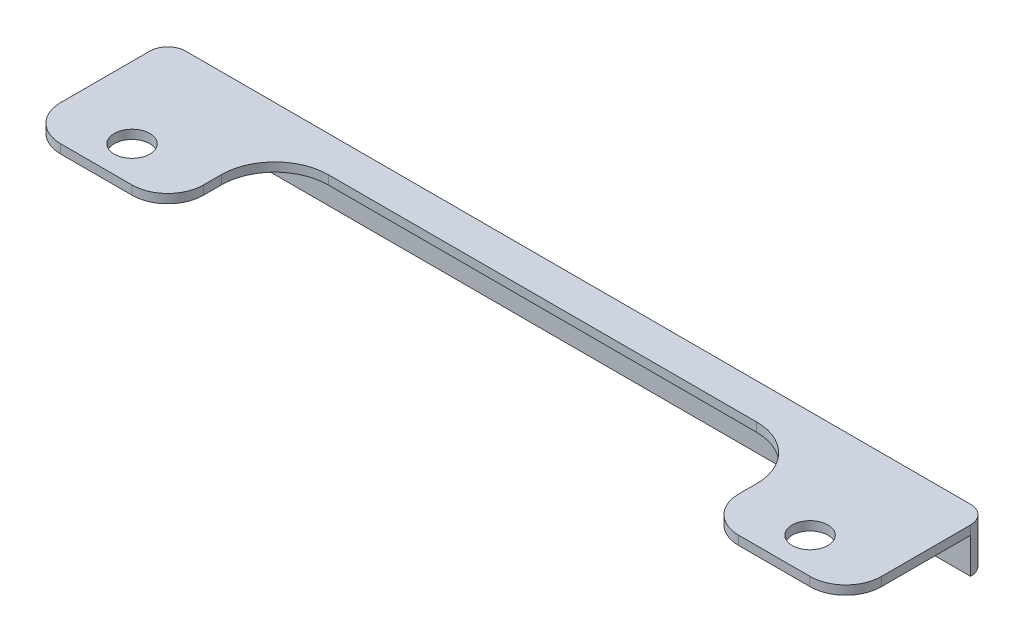
SolidWorks part; units mm, degrees
other "Markup1"
sketch "Sketch13" plane through (162.5103, 0, -104.1871) normal (0.0469, 0.9988, -0.0111) x (0.9947, -0.0457, 0.0919)
ref_plane "Front Plane" through (0, 0, 0) normal (0, 0, 1) x (1, 0, 0)
ref_plane "Top Plane" through (0, 0, 0) normal (0, 1, 0) x (1, 0, 0)
ref_plane "Right Plane" through (0, 0, 0) normal (1, 0, 0) x (0, 0, -1)
sketch "Sketch1" plane through (0, 0, 0) normal (0, 1, 0) x (1, 0, 0)
  line L0 (-88.0488, 103.273) -> (161.9512, 103.273)
  line L1 (-88.0488, 103.273) -> (-88.0488, 53.273)
  line L2 (161.9512, 103.273) -> (161.9512, 53.273)
  line L3 (-88.0488, 53.273) -> (-38.0488, 53.273)
  line L4 (-38.0488, 53.273) -> (-38.0488, 93.273)
  line L5 (36.9512, 136.3536) -> (36.9512, 9.8202) construction
  line L6 (111.9512, 53.273) -> (111.9512, 93.273)
  line L7 (161.9512, 53.273) -> (111.9512, 53.273)
  line L8 (161.9512, 103.273) -> (161.9512, 53.273)
  line L9 (-38.0488, 93.273) -> (111.9512, 93.273)
  dimension "D1" = 250
  dimension "D2" = 50
  dimension "D3" = 50
  dimension "D4" = 50
  dimension "D5" = 40
extrude "Boss-Extrude2" add sketch "Sketch1" against normal blind 40 contours L5 L0 L1 L3 L4 L9 | L0 L5 L9 L6 L7 L2 region at (-48.6258, 0, -82.8884) region at (122.5281, 0, -82.8884)
sketch "Sketch2" plane through (0, 0, -53.273) normal (0, 0, 1) x (1, 0, 0)
  line L1 (-88.0488, 0) -> (-88.0488, -40)
  line L2 (-88.0488, -40) -> (-38.0488, -40)
  line L3 (-38.0488, -40) -> (-38.0488, 0)
  line L4 (-38.0488, 0) -> (-88.0488, 0)
  line L6 (-38.0488, -37.5) -> (-88.0488, -37.5)
  line L7 (-38.0488, -37.5) -> (-38.0488, -2.5)
  line L8 (-38.0488, -2.5) -> (-88.0488, -2.5)
  line L9 (-88.0488, -37.5) -> (-88.0488, -2.5)
  line L10 (-38.0488, -37.5) -> (-88.0488, -2.5) construction
  line L11 (-38.0488, -2.5) -> (-88.0488, -37.5) construction
  point P0 (-63.0488, -20)
  dimension "D1" = 2.5
  dimension "D2" = 2.5
extrude "Cut-Extrude1" cut sketch "Sketch2" against normal blind 45 contours L3 L8 L1 L6 region at (-63.0488, -20, -53.273)
sketch "Sketch3" plane through (0, 0, -53.273) normal (0, 0, 1) x (1, 0, 0)
  line L1 (111.9512, 0) -> (161.9512, 0)
  line L2 (111.9512, 0) -> (111.9512, -40)
  line L3 (111.9512, -40) -> (161.9512, -40)
  line L4 (161.9512, 0) -> (161.9512, -40)
  line L5 (111.9512, -2.5) -> (161.9512, -2.5)
  line L6 (111.9512, -2.5) -> (111.9512, -37.5)
  line L7 (111.9512, -37.5) -> (161.9512, -37.5)
  line L8 (161.9512, -2.5) -> (161.9512, -37.5)
  line L9 (111.9512, -2.5) -> (161.9512, -37.5) construction
  line L10 (111.9512, -37.5) -> (161.9512, -2.5) construction
  point P6 (136.9512, -20)
  dimension "D1" = 2.5
  dimension "D2" = 2.5
extrude "Cut-Extrude2" cut sketch "Sketch3" against normal blind 45 contours L2 L7 L4 L5 region at (136.9512, -20, -53.273)
sketch "Sketch4" plane through (0, 0, -93.273) normal (0, 0, 1) x (1, 0, 0)
  line L0 (-38.0488, 0) -> (-38.0488, -40)
  line L1 (-38.0488, -40) -> (111.9512, -40)
  line L2 (111.9512, -40) -> (111.9512, 0)
  line L3 (111.9512, 0) -> (-38.0488, 0)
  line L5 (-38.0488, -2.5) -> (111.9512, -2.5)
  line L6 (-38.0488, -2.5) -> (-38.0488, -37.5)
  line L7 (-38.0488, -37.5) -> (111.9512, -37.5)
  line L8 (111.9512, -2.5) -> (111.9512, -37.5)
  line M5 (-38.0488, -2.5) -> (-38.0488, -37.5)
  line M9 (111.9512, -37.5) -> (111.9512, -2.5)
  dimension "D1" = 2.5
  dimension "D2" = 2.5
extrude "Cut-Extrude3" cut sketch "Sketch4" against normal blind 5 contours L7 L5 M5 M9 region at (36.9512, -20, -93.273)
sketch "Sketch5" plane through (0, -40, 0) normal (0, -1, 0) x (1, 0, 0)
  line L0 (-38.0488, -78.273) -> (-38.0488, -63.273)
  line L1 (-48.0488, -53.273) -> (-78.0488, -53.273)
  line L2 (-88.0488, -63.273) -> (-88.0488, -95.773)
  line L3 (-80.5488, -103.273) -> (154.4512, -103.273)
  line L4 (161.9512, -95.773) -> (161.9512, -63.273)
  line L5 (151.9512, -53.273) -> (121.9512, -53.273)
  line L6 (111.9512, -63.273) -> (111.9512, -78.273)
  line L7 (96.9512, -93.273) -> (-23.0488, -93.273)
  line L8 (-88.0488, -95.773) -> (-88.0488, -103.273)
  line L9 (-88.0488, -103.273) -> (-80.5488, -103.273)
  line L10 (-88.0488, -63.273) -> (-88.0488, -53.273)
  line L11 (-88.0488, -53.273) -> (-78.0488, -53.273)
  line L12 (-48.0488, -53.273) -> (-38.0488, -53.273)
  line L13 (-38.0488, -53.273) -> (-38.0488, -63.273)
  line L14 (-38.0488, -78.273) -> (-38.0488, -93.273)
  line L15 (-38.0488, -93.273) -> (-23.0488, -93.273)
  line L16 (96.9512, -93.273) -> (111.9512, -93.273)
  line L17 (111.9512, -93.273) -> (111.9512, -78.273)
  line L18 (111.9512, -63.273) -> (111.9512, -53.273)
  line L19 (111.9512, -53.273) -> (121.9512, -53.273)
  line L20 (151.9512, -53.273) -> (161.9512, -53.273)
  line L21 (161.9512, -53.273) -> (161.9512, -63.273)
  line L22 (161.9512, -95.773) -> (161.9512, -103.273)
  line L23 (161.9512, -103.273) -> (154.4512, -103.273)
  arc A0 (161.9512, -63.273) -> (151.9512, -53.273) centre (151.9512, -63.273) ccw
  arc A1 (121.9512, -53.273) -> (111.9512, -63.273) centre (121.9512, -63.273) ccw
  arc A2 (-78.0488, -53.273) -> (-88.0488, -63.273) centre (-78.0488, -63.273) ccw
  arc A3 (-38.0488, -63.273) -> (-48.0488, -53.273) centre (-48.0488, -63.273) ccw
  arc A4 (-38.0488, -78.273) -> (-23.0488, -93.273) centre (-23.0488, -78.273) ccw
  arc A5 (111.9512, -78.273) -> (96.9512, -93.273) centre (96.9512, -78.273) cw
  arc A6 (154.4512, -103.273) -> (161.9512, -95.773) centre (154.4512, -95.773) ccw
  arc A7 (-88.0488, -95.773) -> (-80.5488, -103.273) centre (-80.5488, -95.773) ccw
  point P18 (161.9512, -53.273)
  point P21 (111.9512, -53.273)
  point P24 (-88.0488, -53.273)
  point P27 (-38.0488, -53.273)
  point P30 (-38.0488, -93.273)
  point P33 (111.9512, -93.273)
  point P36 (161.9512, -103.273)
  point P39 (-88.0488, -103.273)
  line M16 (-38.0488, -93.273) -> (-38.0488, -53.273)
  line M17 (-38.0488, -53.273) -> (-88.0488, -53.273)
  line M18 (-88.0488, -53.273) -> (-88.0488, -103.273)
  line M19 (-88.0488, -103.273) -> (161.9512, -103.273)
  line M20 (161.9512, -103.273) -> (161.9512, -53.273)
  line M21 (161.9512, -53.273) -> (111.9512, -53.273)
  line M22 (111.9512, -53.273) -> (111.9512, -93.273)
  dimension "D1" = 10
  dimension "D2" = 15
  dimension "D3" = 7.5
extrude "Cut-Extrude4" cut sketch "Sketch5" against normal blind 50 contours A7 M18 M19 | A2 M17 M18 | A3 M16 M17 | A1 M21 M22 | A0 M20 M21 | A6 M19 M20 region at (-40.2825, -40, -55.5067) region at (-85.8152, -40, -55.5067) region at (114.1848, -40, -55.5067) region at (-86.3736, -40, -101.5978) region at (159.7175, -40, -55.5067) region at (160.2759, -40, -101.5978)
sketch "Sketch8" plane through (0, -40, 0) normal (0, -1, 0) x (1, 0, 0)
  line L0 (111.9512, -63.273) -> (111.9512, -78.273)
  line L1 (96.9512, -93.273) -> (-23.0488, -93.273)
  line L2 (-38.0488, -78.273) -> (-38.0488, -63.273)
  line L3 (96.9512, -93.273) -> (111.9512, -93.273)
  line L4 (111.9512, -93.273) -> (111.9512, -78.273)
  line L5 (-23.0488, -93.273) -> (-38.0488, -93.273)
  line L6 (-38.0488, -93.273) -> (-38.0488, -78.273)
  arc A0 (111.9512, -78.273) -> (96.9512, -93.273) centre (96.9512, -78.273) cw
  arc A1 (-23.0488, -93.273) -> (-38.0488, -78.273) centre (-23.0488, -78.273) cw
  point P10 (111.9512, -93.273)
  point P13 (-38.0488, -93.273)
  line M6 (111.9512, -63.273) -> (111.9512, -93.273)
  line M7 (111.9512, -93.273) -> (-38.0488, -93.273)
  line M8 (-38.0488, -93.273) -> (-38.0488, -63.273)
  dimension "D1" = 15
extrude "Boss-Extrude3" add sketch "Sketch8" against normal blind 2.5 contours A1 M7 M8 | A0 M6 M7 region at (-34.6983, -40, -89.9225) region at (108.6006, -40, -89.9225)
sketch "Sketch9" plane through (0, 0, 0) normal (0, 1, 0) x (1, 0, 0)
  line L0 (-38.0488, 63.273) -> (-38.0488, 78.273)
  line L1 (-23.0488, 93.273) -> (96.9512, 93.273)
  line L2 (111.9512, 78.273) -> (111.9512, 63.273)
  line L3 (-38.0488, 78.273) -> (-38.0488, 93.273)
  line L4 (-38.0488, 93.273) -> (-23.0488, 93.273)
  line L5 (96.9512, 93.273) -> (111.9512, 93.273)
  line L6 (111.9512, 93.273) -> (111.9512, 78.273)
  arc A0 (-38.0488, 78.273) -> (-23.0488, 93.273) centre (-23.0488, 78.273) cw
  arc A1 (96.9512, 93.273) -> (111.9512, 78.273) centre (96.9512, 78.273) cw
  point P10 (-38.0488, 93.273)
  point P13 (111.9512, 93.273)
  line M9 (-38.0488, 63.273) -> (-38.0488, 93.273)
  line M10 (-38.0488, 93.273) -> (111.9512, 93.273)
  line M11 (111.9512, 93.273) -> (111.9512, 63.273)
  dimension "D1" = 15
extrude "Boss-Extrude4" add sketch "Sketch9" against normal blind 2.5 contours A1 M10 M11 | A0 M9 M10 region at (108.6006, 0, -89.9225) region at (-34.6983, 0, -89.9225)
sketch "Sketch10" plane through (0, 0, 0) normal (0, 1, 0) x (1, 0, 0)
  line L0 (-78.0488, 53.273) -> (-48.0488, 53.273) construction
  line L1 (-23.0488, 93.273) -> (96.9512, 93.273) construction
  line L2 (36.9512, 103.273) -> (36.9512, 93.273) construction
  line L3 (-80.5488, 103.273) -> (154.4512, 103.273) construction
  circle A0 centre (-62.6651, 73.273) radius 7.5
  circle A1 centre (136.5675, 73.273) radius 7.5
  dimension "D1" = 15
  dimension "D2" = 20
  dimension "D3" = 20
extrude "Cut-Extrude5" cut sketch "Sketch10" against normal blind 50 contours A0 | A1
sketch "Sketch11" plane through (0, 0, -98.273) normal (0, 0, 1) x (1, 0, 0)
  line L1 (-87.6199, -2.5) -> (161.5222, -2.5)
  line L2 (-87.6199, -2.5) -> (-87.6199, -37.5)
  line L3 (-87.6199, -37.5) -> (161.5222, -37.5)
  line L4 (161.5222, -2.5) -> (161.5222, -37.5)
  line L5 (-87.6199, -12.5) -> (161.5222, -12.5)
  line L6 (-87.6199, -12.5) -> (-87.6199, -16.0665)
  line L8 (161.5222, -12.5) -> (161.5222, -16.0665)
  line M3 (-87.6199, -37.5) -> (161.5222, -37.5)
  line M4 (161.5222, -37.5) -> (161.5222, -2.5)
  line M6 (-87.6199, -2.5) -> (-87.6199, -37.5)
  dimension "D1" = 10
extrude "Cut-Extrude7" cut sketch "Sketch11" against normal blind 10 contours L5 L2 L4 M6 M3 M4 region at (36.9512, -25, -98.273)
sketch "Sketch12" plane through (0, -40, 0) normal (0, -1, 0) x (1, 0, 0)
  line L1 (-88.0488, -53.273) -> (162.5103, -53.273)
  line L2 (-88.0488, -53.273) -> (-88.0488, -104.1871)
  line L3 (-88.0488, -104.1871) -> (162.5103, -104.1871)
  line L4 (162.5103, -53.273) -> (162.5103, -104.1871)
extrude "Cut-Extrude8" cut sketch "Sketch12" against normal blind 10
sketch "Sketch14" plane through (0, 0, 0) normal (0, 1, 0) x (1, 0, 0)
  circle A0 centre (-62.6651, 73.273) radius 7.5
  circle A1 centre (136.5675, 73.273) radius 7.5
extrude "Boss-Extrude5" add sketch "Sketch14" against normal blind 2.5
sketch "Sketch15" plane through (0, 0, 0) normal (0, 1, 0) x (1, 0, 0)
  line L0 (161.9512, 95.773) -> (161.9512, 63.273) construction
  line L1 (-88.0488, 95.773) -> (-88.0488, 63.273) construction
  line L6 (-90.9932, 104.1687) -> (-78.0488, 104.1687)
  line L7 (-90.9932, 104.1687) -> (-90.9932, 52.6329)
  line L8 (-90.9932, 52.6329) -> (-78.0488, 52.6329)
  line L9 (-78.0488, 104.1687) -> (-78.0488, 52.6329)
  line L11 (173.1393, 108.8307) -> (151.9512, 108.8307)
  line L12 (173.1393, 108.8307) -> (173.1393, 48.2197)
  line L13 (173.1393, 48.2197) -> (151.9512, 48.2197)
  line L14 (151.9512, 108.8307) -> (151.9512, 48.2197)
  dimension "D1" = 10
  dimension "D2" = 10
extrude "Cut-Extrude9" cut sketch "Sketch15" against normal blind 50
sketch "Sketch17" plane through (0, 0, 0) normal (0, 1, 0) x (1, 0, 0)
  line L0 (151.9512, 103.273) -> (151.9512, 53.273) construction
  line L1 (-78.0488, 53.273) -> (151.9512, 53.273)
  line L2 (-78.0488, 53.273) -> (-78.0488, 63.273)
  line L3 (-78.0488, 63.273) -> (151.9512, 63.273)
  line L4 (151.9512, 53.273) -> (151.9512, 63.273)
  dimension "D1" = 10
extrude "Cut-Extrude10" cut sketch "Sketch17" against normal blind 50
fillet "Fillet3" radius 5 2 edges at (151.9512, -6.25, -103.273) (-78.0488, -6.25, -103.273)
fillet "Fillet4" radius 10 4 edges at (111.9512, -1.25, -63.273) (151.9512, -1.25, -63.273) (-38.0488, -1.25, -63.273) (-78.0488, -1.25, -63.273)
sketch "Sketch18" plane through (0, -2.5, 0) normal (0, -1, 0) x (1, 0, 0)
  line L0 (141.9512, -63.273) -> (121.9512, -63.273) construction
  line L1 (-48.0488, -63.273) -> (-68.0488, -63.273) construction
  line L2 (111.9512, -73.273) -> (111.9512, -78.273) construction
  line L4 (-78.0488, -73.273) -> (-78.0488, -98.273) construction
  circle A0 centre (131.9512, -73.273) radius 5
  circle A1 centre (-58.0488, -73.273) radius 5
  dimension "D1" = 10
  dimension "D2" = 10
  dimension "D3" = 10
  dimension "D4" = 10
  dimension "D5" = 20
  dimension "D6" = 20
extrude "Cut-Extrude11" cut sketch "Sketch18" against normal blind 50
